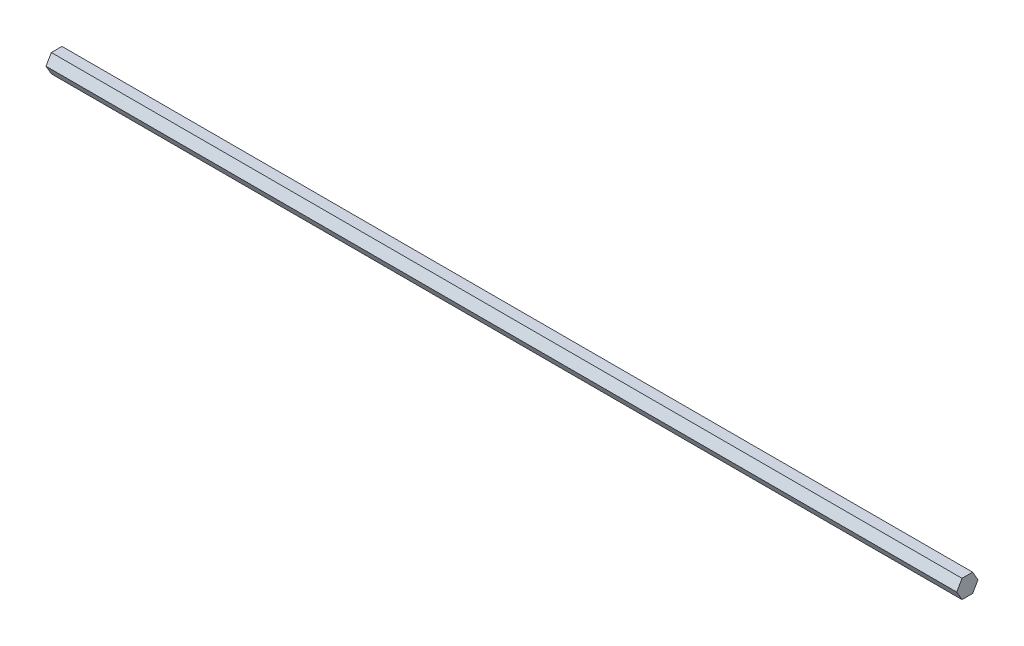
SolidWorks part; units mm, degrees
ref_plane "Front Plane" through (0, 0, 0) normal (0, 0, 1) x (1, 0, 0)
ref_plane "Top Plane" through (0, 0, 0) normal (0, 1, 0) x (1, 0, 0)
ref_plane "Right Plane" through (0, 0, 0) normal (1, 0, 0) x (0, 0, -1)
sketch "Sketch1" plane through (0, 0, 0) normal (1, 0, 0) x (0, 0, -1)
  line L1 (7.3323, 0) -> (3.6662, 6.35)
  line L2 (3.6662, 6.35) -> (-3.6662, 6.35)
  line L3 (-3.6662, 6.35) -> (-7.3323, 0)
  line L4 (-7.3323, 0) -> (-3.6662, -6.35)
  line L5 (-3.6662, -6.35) -> (3.6662, -6.35)
  line L6 (3.6662, -6.35) -> (7.3323, 0)
  circle A0 centre (0, 0) radius 6.35 construction
  dimension "D1" = 12.7
extrude "Boss-Extrude1" add sketch "Sketch1" along normal blind 626.872
